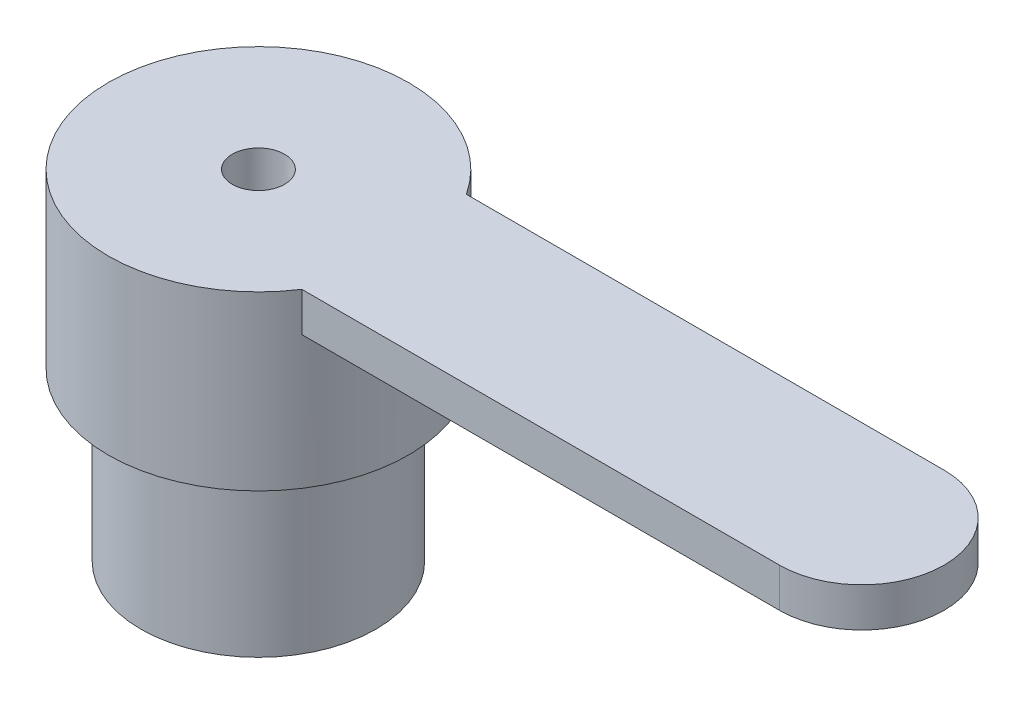
SolidWorks part; units mm, degrees
note: The reader was unsure of these and kept them because the rebuilt part matched: shared geometry of "Sketch1<4>".
ref_plane "Front" through (0, 0, 0) normal (0, 0, 1) x (1, 0, 0)
ref_plane "Top" through (0, 0, 0) normal (0, 1, 0) x (1, 0, 0)
ref_plane "Right" through (0, 0, 0) normal (1, 0, 0) x (0, 0, -1)
sketch "Sketch1" plane through (0, 0, 0) normal (0, 1, 0) x (1, 0, 0)
  line L0 (11.55, -1.575) -> (0, -1.575)
  line L1 (0, 0) -> (0, 2.875) construction
  line L2 (0, -1.575) -> (0, 1.575)
  line L3 (0, 1.575) -> (11.55, 1.575)
  line L4 (0, 0) -> (-10.6498, 0) construction
  circle A0 centre (0, 0) radius 2.875
  arc A1 (11.55, -1.575) -> (11.55, 1.575) centre (11.55, 0) ccw
  point P10 (13.125, 0)
  point P11 (0, 0)
  point P13 (-2.875, 0)
  dimension "D1" = 5.75
  dimension "D2" = 3.15
  dimension "D3" = 16
extrude "Boss-Extrude1" add sketch "Sketch1" against normal blind 2.55 contours A0
extrude "Boss-Extrude2" add sketch "Sketch1<4>" along normal blind 0.75
sketch "Sketch1<4>" plane through (0, 0, 0) normal (0, 1, 0) x (1, 0, 0) same geometry as "Sketch1"
sketch "Sketch2" plane through (0, -2.55, 0) normal (0, -1, 0) x (1, 0, 0)
  circle A0 centre (0, 0) radius 2.25
  dimension "D1" = 4.5
extrude "Boss-Extrude3" add sketch "Sketch2" along normal blind 3.2
sketch "Sketch3" plane through (0, -5.75, 0) normal (0, -1, 0) x (1, 0, 0)
  circle A0 centre (0, 0) radius 0.5
  dimension "D1" = 1
extrude "Cut-Extrude1" cut sketch "Sketch3" against normal through all
